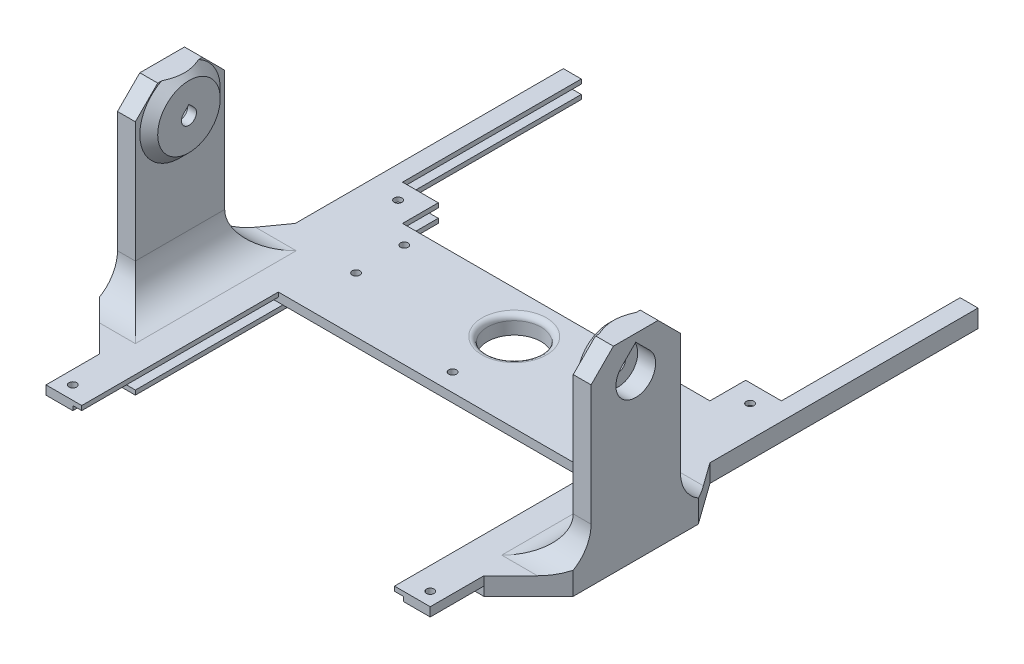
SolidWorks part; units mm, degrees
ref_plane "Alzado" through (0, 0, 0) normal (0, 0, 1) x (1, 0, 0)
ref_plane "Planta" through (0, 0, 0) normal (0, 1, 0) x (1, 0, 0)
ref_plane "Vista lateral" through (0, 0, 0) normal (1, 0, 0) x (0, 0, -1)
sketch "Croquis1" plane through (0, 0, 0) normal (0, 1, 0) x (1, 0, 0)
  line L0 (116, 58) -> (132.5, 35)
  line L8 (116, 88) -> (116, 58)
  line L12 (-132.5, 35) -> (-132.5, -35)
  line L18 (-107.5, -60) -> (-132.5, -35)
  line L22 (-116, 88) -> (-116, 58)
  line L23 (-116, 58) -> (-132.5, 35)
  line L552 (107.5, -60) -> (132.5, -35)
  line L553 (132.5, 35) -> (132.5, -35)
  line L554 (0, 0) -> (0, -155) construction
  line L558 (-80, -60) -> (0, -60) construction
  line L559 (0, -60) -> (80, -60) construction
  line L566 (-132.5, 0) -> (0, 0) construction
  line L567 (0, 0) -> (132.5, 0) construction
  line L569 (0, 101) -> (0, 0) construction
  line L570 (-116, 88) -> (116, 88)
  line L572 (-92.5, -90) -> (-92.5, 40)
  line L573 (-92.5, 40) -> (92.5, 40)
  line L574 (92.5, 40) -> (92.5, -90)
  line L577 (-107.5, -60) -> (-107.5, -90)
  line L578 (-107.5, -90) -> (-92.5, -90)
  line L579 (107.5, -60) -> (107.5, -90)
  line L580 (107.5, -90) -> (92.5, -90)
  point P16 (-132.5, 0)
  dimension "D8" = 25
  dimension "D2" = 232
  dimension "D4" = 30
  dimension "D5" = 30
  dimension "D6" = 130
  dimension "D7" = 23
  dimension "D9" = 25
  dimension "D10" = 15
  dimension "D16" = 265
  dimension "D30" = 70
extrude "Saliente-Extruir2" add sketch "Croquis1" along normal blind 10
sketch "Croquis3" plane through (0, 10, 0) normal (0, 1, 0) x (1, 0, 0)
  line L0 (132.5, 25) -> (122.5, 25)
  line L1 (132.5, -35) -> (132.5, 35) construction
  line L2 (122.5, 25) -> (122.5, -25)
  line L3 (122.5, -25) -> (132.5, -25)
  line L4 (132.5, -25) -> (132.5, 25)
  line L5 (132.5, 35) -> (132.5, 25) construction
  line L6 (132.5, -25) -> (132.5, -35) construction
  line L7 (0, -155) -> (0, -12.7186) construction
  line L10 (0, -135.114) -> (0, 15) construction
  line L11 (0, 64.5) -> (0, -38.3443) construction
  line L12 (-122.5, -25) -> (-132.5, -25)
  line L13 (-122.5, 25) -> (-122.5, -25)
  line L14 (-132.5, 25) -> (-122.5, 25)
  line L15 (-132.5, -25) -> (-132.5, 25)
  dimension "D1" = 10
  dimension "D2" = 50
extrude "Saliente-Extruir4" add sketch "Croquis3" along normal blind 100
sketch "Croquis4" plane through (132.5, 0, 0) normal (1, 0, 0) x (0, 0, -1)
  line L0 (0, 110) -> (0, 90) construction
  line L1 (-25, 110) -> (25, 110) construction
  line L2 (-7.8489, 97.8489) -> (0, 105.6978)
  line L3 (0, 105.6978) -> (7.8489, 97.8489)
  arc A0 (-7.8489, 97.8489) -> (7.8489, 97.8489) centre (0, 90) ccw
  dimension "D1" = 22.2
  dimension "D2" = 20
  dimension "D3" = 90
extrude "Cortar-Extruir1" cut sketch "Croquis4" against normal through all both and the other way through all
sketch "Croquis5" plane through (122.5, 0, 0) normal (-1, 0, 0) x (0, 0, 1)
  line L0 (0, 90) -> (0, 95.9397) construction
  line L1 (-2.9698, 92.9698) -> (0, 95.9397)
  line L2 (0, 95.9397) -> (2.9698, 92.9698)
  circle A0 centre (0, 90) radius 17.5
  arc A1 (-2.9698, 92.9698) -> (2.9698, 92.9698) centre (0, 90) ccw
  dimension "D1" = 8.4
  dimension "D2" = 35
  dimension "D3" = 90
extrude "Saliente-Extruir5" add sketch "Croquis5" along normal blind 5
chamfer "Chaflán1" distance 5 angle 45 1 edges at (122.5, 90, -17.5)
sketch "Croquis6" plane through (-122.5, 0, 0) normal (1, 0, 0) x (0, 0, -1)
  line L0 (0, 90) -> (0, 95.9397) construction
  line L1 (-2.9698, 92.9698) -> (0, 95.9397)
  line L2 (0, 95.9397) -> (2.9699, 92.9698)
  arc A0 (-2.9698, 92.9698) -> (2.9699, 92.9698) centre (0, 90) ccw
  circle A1 centre (0, 90) radius 17.5
  dimension "D1" = 35
  dimension "D2" = 8.4
  dimension "D3" = 90
extrude "Saliente-Extruir6" add sketch "Croquis6" along normal blind 5
chamfer "Chaflán3" distance 12.5 angle 45 4 edges at (-127.5, 110, -25) (-127.5, 110, 25) (127.5, 110, -25) (127.5, 110, 25)
chamfer "Chaflán2" distance 5 angle 45 1 edges at (-122.5, 90, 17.5)
sketch "Croquis8" plane through (-117.5, 0, 0) normal (1, 0, 0) x (0, 0, -1)
  line L1 (-7.5, 97.5) -> (7.5, 97.5)
  line L2 (-7.5, 97.5) -> (-7.5, 82.5)
  line L3 (-7.5, 82.5) -> (7.5, 82.5)
  line L4 (7.5, 97.5) -> (7.5, 82.5)
  line L5 (-7.5, 97.5) -> (7.5, 82.5) construction
  line L6 (-7.5, 82.5) -> (7.5, 97.5) construction
  circle A0 centre (0, 90) radius 4.2
  dimension "D2" = 8.4
  dimension "D1" = 15
extrude "Cortar-Extruir3" [suppressed] cut sketch "Croquis8" against normal blind 2.5
fillet "Redondeo1" radius 20 6 edges at (-127.5, 10, -25) (-127.5, 10, 25) (-122.5, 10, 0) (122.5, 10, 0) (127.5, 10, -25) (127.5, 10, 25)
sketch "Croquis14" plane through (0, 0, -88) normal (0, 0, -1) x (-1, 0, 0)
  line L0 (-86, 10) -> (-116, 10)
  line L1 (-116, 10) -> (-116, 0)
  line L2 (-116, 0) -> (-86, 0)
  line L3 (-116, 0) -> (116, 0) construction
  line L4 (-86, 0) -> (-86, 2.5)
  line L5 (-86, 2.5) -> (-111, 2.5)
  line L6 (-111, 2.5) -> (-111, 7.5)
  line L7 (-111, 7.5) -> (-86, 7.5)
  line L8 (-86, 7.5) -> (-86, 10)
  line L9 (0, 0) -> (0, 10) construction
  line L10 (-116, 10) -> (116, 10) construction
  line L11 (111, 7.5) -> (86, 7.5)
  line L12 (111, 2.5) -> (111, 7.5)
  line L13 (86, 2.5) -> (111, 2.5)
  line L14 (86, 0) -> (86, 2.5)
  line L15 (116, 0) -> (86, 0)
  line L16 (116, 10) -> (116, 0)
  line L17 (86, 10) -> (116, 10)
  line L18 (86, 7.5) -> (86, 10)
  dimension "D1" = 30
  dimension "D2" = 5
  dimension "D3" = 2.5
extrude "Saliente-Extruir9" add sketch "Croquis14" along normal blind 20
sketch "Croquis7" plane through (117.5, 0, 0) normal (-1, 0, 0) x (0, 0, 1)
  line L1 (-7.5, 97.5) -> (7.5, 97.5)
  line L2 (-7.5, 97.5) -> (-7.5, 82.5)
  line L3 (-7.5, 82.5) -> (7.5, 82.5)
  line L4 (7.5, 97.5) -> (7.5, 82.5)
  line L5 (-7.5, 97.5) -> (7.5, 82.5) construction
  line L6 (-7.5, 82.5) -> (7.5, 97.5) construction
  circle A0 centre (0, 90) radius 4.2
  dimension "D2" = 8.4
  dimension "D1" = 15
extrude "Cortar-Extruir2" [suppressed] cut sketch "Croquis7" against normal blind 2.5
sketch "Croquis9" plane through (0, 10, 0) normal (0, 1, 0) x (1, 0, 0)
  line L0 (0, 0) -> (0, 64.5) construction
  line L1 (0, 64.5) -> (0, 88) construction
  line L2 (86, 88) -> (-86, 88) construction
  line L3 (0, 78) -> (-75, 78) construction
  line L4 (-75, 78) -> (-75, 88) construction
  line L5 (0, 64.5) -> (-49.1848, 64.5) construction
  line L6 (100, -90) -> (100, -75) construction
  line L7 (92.5, -90) -> (107.5, -90) construction
  line L8 (86, 98) -> (111, 98) construction
  line L9 (86, 108) -> (86, 88) construction
  circle A0 centre (0, 64.5) radius 15
  circle A1 centre (-75, 78) radius 2.15
  circle A2 centre (75, 78) radius 2.15
  circle A3 centre (75, 51) radius 2.15
  circle A4 centre (-75, 51) radius 2.15
  circle A5 centre (100, -82.5) radius 2.15
  circle A6 centre (-100, -82.5) radius 2.15
  circle A7 centre (98.5, 98) radius 2.15
  circle A8 centre (-98.5, 98) radius 2.15
  dimension "D3" = 30
  dimension "D6" = 4.3
  dimension "D8" = 4.3
  dimension "D10" = 4.3
  dimension "D1" = 64.5
  dimension "D2" = 23.5
  dimension "D4" = 13.5
  dimension "D5" = 75
  dimension "D7" = 15
  dimension "D9" = 25
extrude "Cortar-Extruir4" cut sketch "Croquis9" against normal blind 10
fillet "Redondeo2" radius 3 1 edges at (0, 10, -49.5)
sketch "Croquis11" plane through (0, 10, 0) normal (0, 1, 0) x (1, 0, 0)
  line L1 (-92.5, 40) -> (92.5, 40)
  line L8 (-92.5, 40) -> (-92.5, 20)
  line L9 (-92.5, -90) -> (-92.5, 40) construction
  line L10 (-92.5, 20) -> (92.5, 20)
  line L11 (92.5, 40) -> (92.5, -90) construction
  line L12 (92.5, 20) -> (92.5, 40)
  line L13 (0, 20) -> (0, 40) construction
  circle A0 centre (0, 30) radius 2.15
  dimension "D2" = 4.3
  dimension "D1" = 20
extrude "Saliente-Extruir7" add sketch "Croquis11" against normal blind 5
sketch "Croquis12" plane through (0, 0, 90) normal (0, 0, 1) x (1, 0, 0)
  line L0 (-92.5, 10) -> (-87.5, 10)
  line L1 (-92.5, 10) -> (92.5, 10) construction
  line L2 (-87.5, 10) -> (-87.5, 7.5)
  line L3 (-87.5, 7.5) -> (-92.5, 7.5)
  line L4 (-92.5, 5) -> (-92.5, 10) construction
  line L5 (-92.5, 7.5) -> (-92.5, 5) construction
  line L6 (-92.5, 10) -> (-92.5, 0) construction
  line L7 (-92.5, 2.5) -> (-87.5, 2.5)
  line L8 (-87.5, 2.5) -> (-87.5, 0)
  line L9 (-92.5, 0) -> (92.5, 0) construction
  line L10 (-87.5, 0) -> (-92.5, 0)
  line L11 (-92.5, 0) -> (-92.5, 2.5)
  line L12 (-92.5, 5) -> (-92.5, 2.5) construction
  line L13 (-92.5, 10) -> (-92.5, 7.5)
  line L14 (0, 0) -> (0, 23.8317) construction
  line L15 (92.5, 0) -> (92.5, 2.5)
  line L16 (87.5, 0) -> (92.5, 0)
  line L17 (87.5, 2.5) -> (87.5, 0)
  line L18 (92.5, 2.5) -> (87.5, 2.5)
  line L19 (92.5, 10) -> (87.5, 10)
  line L20 (87.5, 10) -> (87.5, 7.5)
  line L21 (87.5, 7.5) -> (92.5, 7.5)
  line L22 (92.5, 10) -> (92.5, 7.5)
  dimension "D1" = 2.5
  dimension "D2" = 5
extrude "Saliente-Extruir8" add sketch "Croquis12" against normal up to surface (130 mm away) up to face at (0, 2.5, -40)
sketch "Croquis13" plane through (0, 0, 90) normal (0, 0, 1) x (1, 0, 0)
  line L0 (-92.5, 5) -> (-107.5, 5)
  line L1 (-92.5, 7.5) -> (-92.5, 2.5) construction
  line L2 (-107.5, 10) -> (-107.5, 0) construction
  line L3 (-107.5, 5) -> (-107.5, 0)
  line L4 (-107.5, 0) -> (-87.5, 0)
  line L5 (-87.5, 0) -> (-87.5, 5)
  line L6 (-92.5, 5) -> (92.5, 5) construction
  line L7 (-87.5, 5) -> (-92.5, 5)
  line L8 (0, 0) -> (0, 28.3473) construction
  line L9 (87.5, 0) -> (87.5, 5)
  line L10 (107.5, 0) -> (87.5, 0)
  line L11 (107.5, 5) -> (107.5, 0)
  line L12 (92.5, 5) -> (107.5, 5)
  line L13 (87.5, 5) -> (92.5, 5)
extrude "Cortar-Extruir5" cut sketch "Croquis13" against normal blind 30
sketch "Croquis15" plane through (0, 0, -108) normal (0, 0, -1) x (-1, 0, 0)
  line L0 (-106, 2.5) -> (-111, 2.5)
  line L1 (-86, 2.5) -> (-111, 2.5) construction
  line L2 (-111, 2.5) -> (-111, 7.5)
  line L3 (-111, 7.5) -> (-106, 7.5)
  line L4 (-111, 7.5) -> (-86, 7.5) construction
  line L5 (-106, 7.5) -> (-106, 10)
  line L6 (-86, 10) -> (-116, 10) construction
  line L7 (-106, 10) -> (-116, 10)
  line L8 (-116, 10) -> (-116, 0)
  line L9 (-116, 0) -> (-106, 0)
  line L10 (-116, 0) -> (-86, 0) construction
  line L11 (-106, 0) -> (-106, 2.5)
  line L12 (0, 0) -> (0, 6.7597) construction
  line L13 (116, 0) -> (106, 0)
  line L14 (116, 10) -> (116, 0)
  line L15 (106, 10) -> (116, 10)
  line L16 (106, 7.5) -> (106, 10)
  line L17 (111, 7.5) -> (106, 7.5)
  line L18 (111, 2.5) -> (111, 7.5)
  line L19 (106, 2.5) -> (111, 2.5)
  line L20 (106, 0) -> (106, 2.5)
  dimension "D1" = 5
  dimension "D2" = 5
extrude "Saliente-Extruir10" add sketch "Croquis15" along normal blind 100
